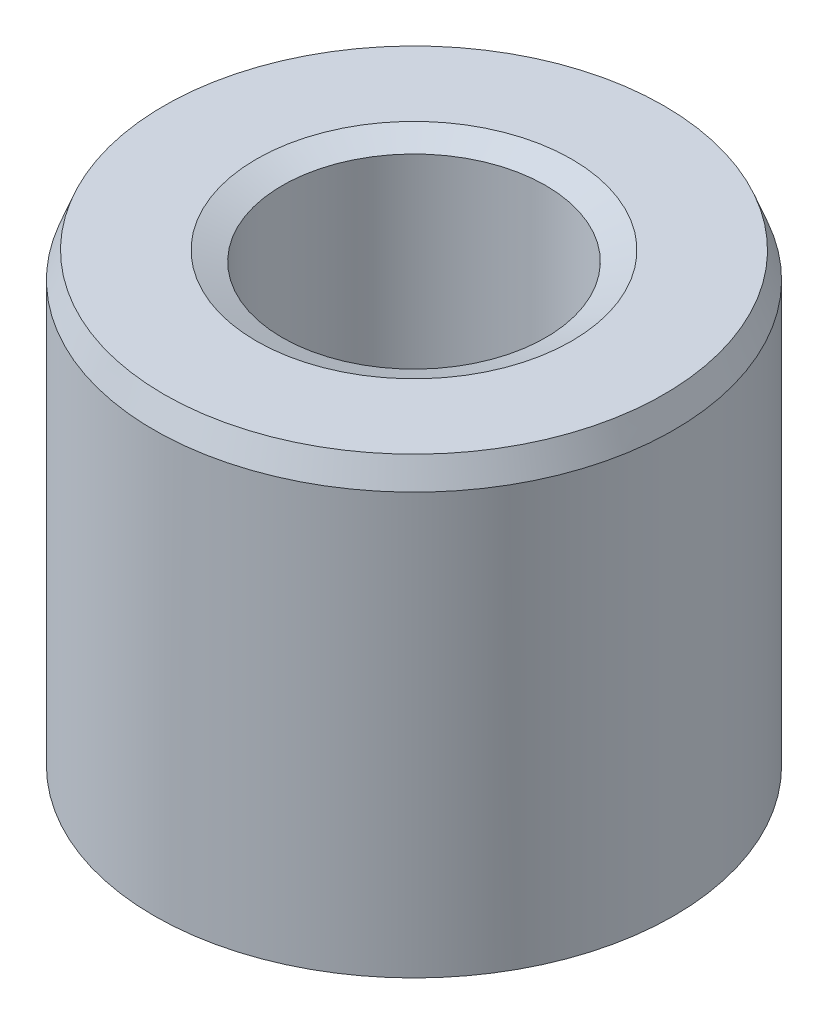
SolidWorks part; units mm, degrees
ref_plane "Front Plane" through (0, 0, 0) normal (0, 0, 1) x (1, 0, 0)
ref_plane "Top Plane" through (0, 0, 0) normal (0, 1, 0) x (1, 0, 0)
ref_plane "Right Plane" through (0, 0, 0) normal (1, 0, 0) x (0, 0, -1)
sketch "Sketch1" plane through (0, 0, 0) normal (0, 1, 0) x (1, 0, 0)
  circle A0 centre (0, 0) radius 30
  dimension "SLEEVE_OD" = 60
extrude "Boss-Extrude1" add sketch "Sketch1" along normal blind 52.6918
sketch "Sketch2" plane through (0, 0, 0) normal (0, 1, 0) x (1, 0, 0)
  circle A0 centre (0, 0) radius 15.2075
  dimension "BORE_D" = 30.415
extrude "Cut-Extrude1" cut sketch "Sketch2" along normal through all
chamfer "Chamfer1" distance 2.987 angle 21.001 4 edges at (0, 52.6918, 15.2075) (0, 0, 15.2075) (0, 0, 30) (0, 52.6918, 30) first distance on face at (0, 52.6918, 15.2075) first distance on face at (0, 0, 15.2075) first distance on face at (0, 52.6918, 30)
